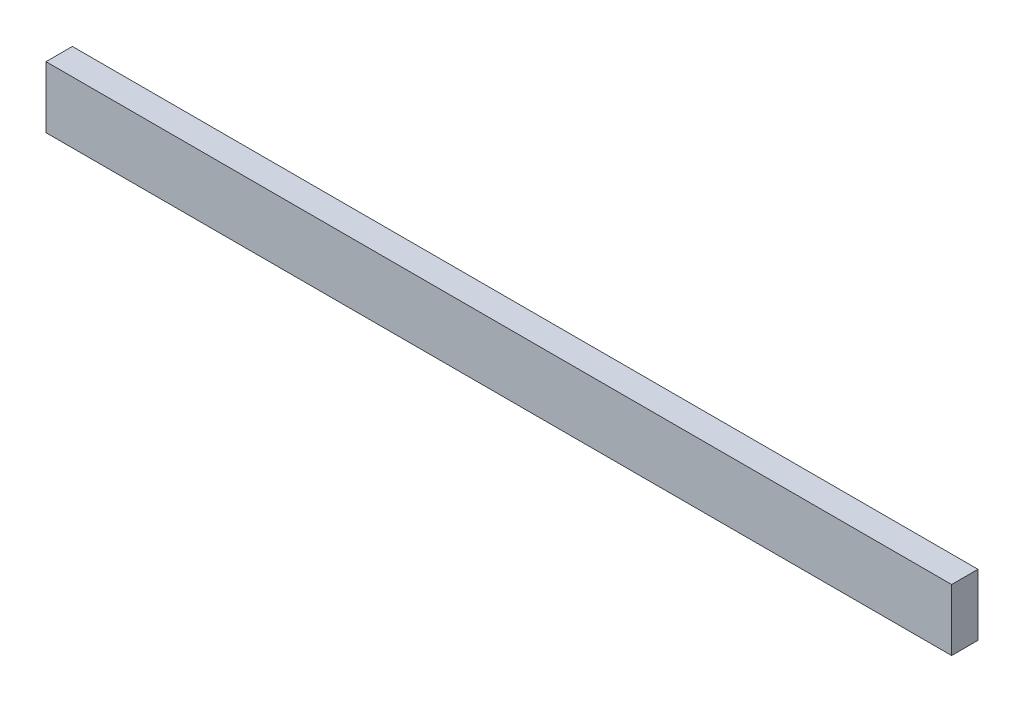
SolidWorks part; units mm, degrees
ref_plane "Front Plane" through (0, 0, 0) normal (0, 0, 1) x (1, 0, 0)
ref_plane "Top Plane" through (0, 0, 0) normal (0, 1, 0) x (1, 0, 0)
ref_plane "Right Plane" through (0, 0, 0) normal (1, 0, 0) x (0, 0, -1)
sketch "Sketch1" plane through (0, 0, 0) normal (1, 0, 0) x (0, 0, -1)
  line L1 (-19.05, -44.45) -> (19.05, -44.45)
  line L2 (-19.05, -44.45) -> (-19.05, 44.45)
  line L3 (-19.05, 44.45) -> (19.05, 44.45)
  line L4 (19.05, -44.45) -> (19.05, 44.45)
  line L5 (-19.05, -44.45) -> (19.05, 44.45) construction
  line L6 (-19.05, 44.45) -> (19.05, -44.45) construction
  point P0 (0, 0)
  dimension "D1" = 88.9
  dimension "D2" = 38.1
extrude "Boss-Extrude1" add sketch "Sketch1" along normal blind 1308.1
